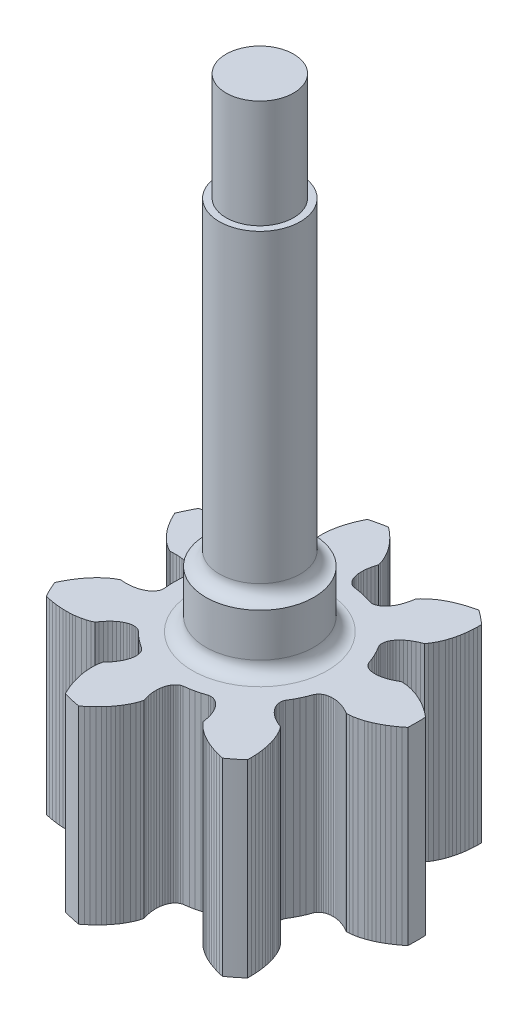
SolidWorks part; units mm, degrees
ref_plane "Front Plane" through (0, 0, 0) normal (0, 0, 1) x (1, 0, 0)
ref_plane "Top Plane" through (0, 0, 0) normal (0, 1, 0) x (1, 0, 0)
ref_plane "Right Plane" through (0, 0, 0) normal (1, 0, 0) x (0, 0, -1)
sketch "Sketch1" plane through (0, 0, 0) normal (0, 1, 0) x (1, 0, 0)
  circle A0 centre (0, 0) radius 2
  dimension "D1" = 4
extrude "Boss-Extrude1" add sketch "Sketch1" along normal blind 2.1
sketch "Sketch2" plane through (0, 2.1, 0) normal (0, 1, 0) x (1, 0, 0)
  circle A0 centre (0, 0) radius 1.5
  dimension "D1" = 3
extrude "Boss-Extrude3" add sketch "Sketch2" along normal blind 15.8
sketch "Sketch4" plane through (0, 0, 0) normal (0, -1, 0) x (1, 0, 0)
  line L420 (-1.6777, -5.4575) -> (-1.7402, -5.3144)
  line L421 (-1.7402, -5.3144) -> (-1.7939, -5.1757)
  line L422 (-1.7939, -5.1757) -> (-1.8392, -5.0423)
  line L423 (-1.8392, -5.0423) -> (-1.8764, -4.916)
  line L424 (-1.8764, -4.916) -> (-1.9071, -4.7932)
  line L425 (-1.9071, -4.7932) -> (-1.9311, -4.676)
  line L426 (-1.9311, -4.676) -> (-1.9488, -4.5668)
  line L427 (-1.9488, -4.5668) -> (-1.961, -4.464)
  line L428 (-1.961, -4.464) -> (-1.9715, -4.2798)
  line L429 (-1.9715, -4.2798) -> (-1.9674, -4.1246)
  line L430 (-1.9674, -4.1246) -> (-1.9537, -4.0009)
  line L431 (-1.9537, -4.0009) -> (-1.9303, -3.8867)
  line L432 (-1.9303, -3.8867) -> (-1.8594, -3.8097)
  line L433 (-1.8594, -3.8097) -> (-1.7784, -3.7125)
  line L434 (-1.7784, -3.7125) -> (-1.7087, -3.6155)
  line L435 (-1.7087, -3.6155) -> (-1.6501, -3.5195)
  line L436 (-1.6501, -3.5195) -> (-1.6023, -3.4251)
  line L437 (-1.6023, -3.4251) -> (-1.5652, -3.3333)
  line L438 (-1.5652, -3.3333) -> (-1.5384, -3.2446)
  line L439 (-1.5384, -3.2446) -> (-1.5215, -3.1597)
  line L440 (-1.5215, -3.1597) -> (-1.5143, -3.0795)
  line L441 (-1.5143, -3.0795) -> (-1.5162, -3.0043)
  line L442 (-1.5162, -3.0043) -> (-1.5269, -2.935)
  line L443 (-1.5269, -2.935) -> (-1.5457, -2.8721)
  line L444 (-1.5457, -2.8721) -> (-1.5723, -2.8162)
  line L445 (-1.5723, -2.8162) -> (-1.606, -2.7677)
  line L446 (-1.606, -2.7677) -> (-1.6572, -2.7183)
  line L447 (-1.6572, -2.7183) -> (-1.8447, -2.5928)
  line L448 (-1.8447, -2.5928) -> (-1.984, -2.4878)
  line L449 (-1.984, -2.4878) -> (-2.1173, -2.3754)
  line L450 (-2.1173, -2.3754) -> (-2.2814, -2.2205)
  line L451 (-2.2814, -2.2205) -> (-2.341, -2.1815)
  line L452 (-2.341, -2.1815) -> (-2.3957, -2.1595)
  line L453 (-2.3957, -2.1595) -> (-2.4562, -2.146)
  line L454 (-2.4562, -2.146) -> (-2.5217, -2.1417)
  line L455 (-2.5217, -2.1417) -> (-2.5917, -2.1467)
  line L456 (-2.5917, -2.1467) -> (-2.6653, -2.1615)
  line L457 (-2.6653, -2.1615) -> (-2.742, -2.1865)
  line L458 (-2.742, -2.1865) -> (-2.8209, -2.2218)
  line L459 (-2.8209, -2.2218) -> (-2.9014, -2.2676)
  line L460 (-2.9014, -2.2676) -> (-2.9827, -2.3243)
  line L461 (-2.9827, -2.3243) -> (-3.0641, -2.3918)
  line L462 (-3.0641, -2.3918) -> (-3.1447, -2.4703)
  line L463 (-3.1447, -2.4703) -> (-3.2237, -2.5599)
  line L464 (-3.2237, -2.5599) -> (-3.3005, -2.6605)
  line L465 (-3.3005, -2.6605) -> (-3.3598, -2.7467)
  line L466 (-3.3598, -2.7467) -> (-3.4659, -2.795)
  line L467 (-3.4659, -2.795) -> (-3.5835, -2.8358)
  line L468 (-3.5835, -2.8358) -> (-3.7338, -2.8744)
  line L469 (-3.7338, -2.8744) -> (-3.9158, -2.9052)
  line L470 (-3.9158, -2.9052) -> (-4.0187, -2.9161)
  line L471 (-4.0187, -2.9161) -> (-4.1291, -2.9232)
  line L472 (-4.1291, -2.9232) -> (-4.2487, -2.9258)
  line L473 (-4.2487, -2.9258) -> (-4.3752, -2.9233)
  line L474 (-4.3752, -2.9233) -> (-4.5067, -2.9151)
  line L475 (-4.5067, -2.9151) -> (-4.6468, -2.9006)
  line L476 (-4.6468, -2.9006) -> (-4.794, -2.8791)
  line L477 (-4.794, -2.8791) -> (-4.9474, -2.85)
  line L478 (-4.9474, -2.85) -> (-5.0902, -2.8167)
  line L479 (-5.3759, -2.2235) -> (-5.3129, -2.0911)
  line L480 (-5.3129, -2.0911) -> (-5.2399, -1.953)
  line L481 (-5.2399, -1.953) -> (-5.165, -1.8245)
  line L482 (-5.165, -1.8245) -> (-5.089, -1.7059)
  line L483 (-5.089, -1.7059) -> (-5.0134, -1.5981)
  line L484 (-5.0134, -1.5981) -> (-4.9365, -1.4976)
  line L485 (-4.9365, -1.4976) -> (-4.8599, -1.4057)
  line L486 (-4.8599, -1.4057) -> (-4.7855, -1.3238)
  line L487 (-4.7855, -1.3238) -> (-4.7128, -1.2502)
  line L488 (-4.7128, -1.2502) -> (-4.5753, -1.1271)
  line L489 (-4.5753, -1.1271) -> (-4.4514, -1.0336)
  line L490 (-4.4514, -1.0336) -> (-4.3462, -0.9671)
  line L491 (-4.3462, -0.9671) -> (-4.2422, -0.9142)
  line L492 (-4.2422, -0.9142) -> (-4.1379, -0.9217)
  line L493 (-4.1379, -0.9217) -> (-4.0114, -0.9244)
  line L494 (-4.0114, -0.9244) -> (-3.8921, -0.9184)
  line L495 (-3.8921, -0.9184) -> (-3.7804, -0.9043)
  line L496 (-3.7804, -0.9043) -> (-3.6769, -0.8828)
  line L497 (-3.6769, -0.8828) -> (-3.5819, -0.8546)
  line L498 (-3.5819, -0.8546) -> (-3.4959, -0.8203)
  line L499 (-3.4959, -0.8203) -> (-3.4191, -0.7805)
  line L500 (-3.4191, -0.7805) -> (-3.3518, -0.7361)
  line L501 (-3.3518, -0.7361) -> (-3.2942, -0.6878)
  line L502 (-3.2942, -0.6878) -> (-3.2467, -0.6363)
  line L503 (-3.2467, -0.6363) -> (-3.2093, -0.5823)
  line L504 (-3.2093, -0.5823) -> (-3.1821, -0.5267)
  line L505 (-3.1821, -0.5267) -> (-3.1652, -0.4701)
  line L506 (-3.1652, -0.4701) -> (-3.1585, -0.3992)
  line L507 (-3.1585, -0.3992) -> (-3.1773, -0.1744)
  line L508 (-3.1773, -0.1744) -> (-3.1821, 0)
  line L509 (-3.1821, 0) -> (-3.1773, 0.1743)
  line L510 (-3.1773, 0.1743) -> (-3.1585, 0.3991)
  line L511 (-3.1585, 0.3991) -> (-3.1652, 0.47)
  line L512 (-3.1652, 0.47) -> (-3.1821, 0.5266)
  line L513 (-3.1821, 0.5266) -> (-3.2093, 0.5822)
  line L514 (-3.2093, 0.5822) -> (-3.2467, 0.6362)
  line L515 (-3.2467, 0.6362) -> (-3.2942, 0.6877)
  line L516 (-3.2942, 0.6877) -> (-3.3518, 0.7361)
  line L517 (-3.3518, 0.7361) -> (-3.4191, 0.7805)
  line L518 (-3.4191, 0.7805) -> (-3.4959, 0.8202)
  line L519 (-3.4959, 0.8202) -> (-3.5819, 0.8545)
  line L520 (-3.5819, 0.8545) -> (-3.6769, 0.8828)
  line L521 (-3.6769, 0.8828) -> (-3.7804, 0.9043)
  line L522 (-3.7804, 0.9043) -> (-3.8921, 0.9183)
  line L523 (-3.8921, 0.9183) -> (-4.0114, 0.9243)
  line L524 (-4.0114, 0.9243) -> (-4.1379, 0.9216)
  line L525 (-4.1379, 0.9216) -> (-4.2422, 0.9142)
  line L526 (-4.2422, 0.9142) -> (-4.3462, 0.967)
  line L527 (-4.3462, 0.967) -> (-4.4514, 1.0335)
  line L528 (-4.4514, 1.0335) -> (-4.5753, 1.127)
  line L529 (-4.5753, 1.127) -> (-4.7128, 1.2501)
  line L530 (-4.7128, 1.2501) -> (-4.7855, 1.3238)
  line L531 (-4.7855, 1.3238) -> (-4.8599, 1.4056)
  line L532 (-4.8599, 1.4056) -> (-4.9365, 1.4975)
  line L533 (-4.9365, 1.4975) -> (-5.0134, 1.598)
  line L534 (-5.0134, 1.598) -> (-5.089, 1.7059)
  line L535 (-5.089, 1.7059) -> (-5.165, 1.8244)
  line L536 (-5.165, 1.8244) -> (-5.2399, 1.9529)
  line L537 (-5.2399, 1.9529) -> (-5.3129, 2.0911)
  line L538 (-5.3129, 2.0911) -> (-5.3759, 2.2234)
  line L539 (-5.0902, 2.8167) -> (-4.9474, 2.8499)
  line L540 (-4.9474, 2.8499) -> (-4.794, 2.879)
  line L541 (-4.794, 2.879) -> (-4.6468, 2.9005)
  line L542 (-4.6468, 2.9005) -> (-4.5067, 2.9151)
  line L543 (-4.5067, 2.9151) -> (-4.3752, 2.9232)
  line L544 (-4.3752, 2.9232) -> (-4.2487, 2.9257)
  line L545 (-4.2487, 2.9257) -> (-4.1291, 2.9231)
  line L546 (-4.1291, 2.9231) -> (-4.0187, 2.916)
  line L547 (-4.0187, 2.916) -> (-3.9158, 2.9051)
  line L548 (-3.9158, 2.9051) -> (-3.7338, 2.8743)
  line L549 (-3.7338, 2.8743) -> (-3.5835, 2.8358)
  line L550 (-3.5835, 2.8358) -> (-3.4659, 2.7949)
  line L551 (-3.4659, 2.7949) -> (-3.3598, 2.7466)
  line L552 (-3.3598, 2.7466) -> (-3.3005, 2.6604)
  line L553 (-3.3005, 2.6604) -> (-3.2237, 2.5598)
  line L554 (-3.2237, 2.5598) -> (-3.1447, 2.4703)
  line L555 (-3.1447, 2.4703) -> (-3.0641, 2.3918)
  line L556 (-3.0641, 2.3918) -> (-2.9827, 2.3242)
  line L557 (-2.9827, 2.3242) -> (-2.9014, 2.2676)
  line L558 (-2.9014, 2.2676) -> (-2.8209, 2.2217)
  line L559 (-2.8209, 2.2217) -> (-2.742, 2.1864)
  line L560 (-2.742, 2.1864) -> (-2.6653, 2.1615)
  line L561 (-2.6653, 2.1615) -> (-2.5917, 2.1466)
  line L562 (-2.5917, 2.1466) -> (-2.5217, 2.1416)
  line L563 (-2.5217, 2.1416) -> (-2.4562, 2.146)
  line L564 (-2.4562, 2.146) -> (-2.3957, 2.1594)
  line L565 (-2.3957, 2.1594) -> (-2.341, 2.1815)
  line L566 (-2.341, 2.1815) -> (-2.2814, 2.2205)
  line L567 (-2.2814, 2.2205) -> (-2.1173, 2.3753)
  line L568 (-2.1173, 2.3753) -> (-1.984, 2.4878)
  line L569 (-1.984, 2.4878) -> (-1.8447, 2.5927)
  line L570 (-1.8447, 2.5927) -> (-1.6572, 2.7182)
  line L571 (-1.6572, 2.7182) -> (-1.606, 2.7676)
  line L572 (-1.606, 2.7676) -> (-1.5723, 2.8161)
  line L573 (-1.5723, 2.8161) -> (-1.5457, 2.8721)
  line L574 (-1.5457, 2.8721) -> (-1.5269, 2.935)
  line L575 (-1.5269, 2.935) -> (-1.5162, 3.0043)
  line L576 (-1.5162, 3.0043) -> (-1.5143, 3.0794)
  line L577 (-1.5143, 3.0794) -> (-1.5215, 3.1597)
  line L578 (-1.5215, 3.1597) -> (-1.5384, 3.2445)
  line L579 (-1.5384, 3.2445) -> (-1.5652, 3.3332)
  line L580 (-1.5652, 3.3332) -> (-1.6023, 3.4251)
  line L581 (-1.6023, 3.4251) -> (-1.6501, 3.5194)
  line L582 (-1.6501, 3.5194) -> (-1.7087, 3.6154)
  line L583 (-1.7087, 3.6154) -> (-1.7784, 3.7125)
  line L584 (-1.7784, 3.7125) -> (-1.8594, 3.8097)
  line L585 (-1.8594, 3.8097) -> (-1.9303, 3.8866)
  line L586 (-1.9303, 3.8866) -> (-1.9537, 4.0009)
  line L587 (-1.9537, 4.0009) -> (-1.9674, 4.1246)
  line L588 (-1.9674, 4.1246) -> (-1.9715, 4.2797)
  line L589 (-1.9715, 4.2797) -> (-1.961, 4.464)
  line L590 (-1.961, 4.464) -> (-1.9488, 4.5668)
  line L591 (-1.9488, 4.5668) -> (-1.9311, 4.6759)
  line L592 (-1.9311, 4.6759) -> (-1.9071, 4.7932)
  line L593 (-1.9071, 4.7932) -> (-1.8764, 4.9159)
  line L594 (-1.8764, 4.9159) -> (-1.8392, 5.0423)
  line L595 (-1.8392, 5.0423) -> (-1.7939, 5.1756)
  line L596 (-1.7939, 5.1756) -> (-1.7402, 5.3143)
  line L597 (-1.7402, 5.3143) -> (-1.6777, 5.4575)
  line L598 (-1.6777, 5.4575) -> (-1.6135, 5.5893)
  line L599 (-0.9715, 5.7358) -> (-0.8565, 5.6449)
  line L600 (-0.8565, 5.6449) -> (-0.7381, 5.543)
  line L601 (-0.7381, 5.543) -> (-0.6295, 5.4414)
  line L602 (-0.6295, 5.4414) -> (-0.5308, 5.3409)
  line L603 (-0.5308, 5.3409) -> (-0.4425, 5.2432)
  line L604 (-0.4425, 5.2432) -> (-0.3616, 5.1459)
  line L605 (-0.3616, 5.1459) -> (-0.2891, 5.0507)
  line L606 (-0.2891, 5.0507) -> (-0.2258, 4.96)
  line L607 (-0.2258, 4.96) -> (-0.1702, 4.8727)
  line L608 (-0.1702, 4.8727) -> (-0.0808, 4.7113)
  line L609 (-0.0808, 4.7113) -> (-0.0172, 4.5697)
  line L610 (-0.0172, 4.5697) -> (0.0242, 4.4523)
  line L611 (0.0242, 4.4523) -> (0.0526, 4.3392)
  line L612 (0.0526, 4.3392) -> (0.0222, 4.2391)
  line L613 (0.0222, 4.2391) -> (-0.0086, 4.1164)
  line L614 (-0.0086, 4.1164) -> (-0.0293, 3.9987)
  line L615 (-0.0293, 3.9987) -> (-0.0405, 3.8868)
  line L616 (-0.0405, 3.8868) -> (-0.0426, 3.7811)
  line L617 (-0.0426, 3.7811) -> (-0.0362, 3.6822)
  line L618 (-0.0362, 3.6822) -> (-0.0218, 3.5907)
  line L619 (-0.0218, 3.5907) -> (-0.0002, 3.5069)
  line L620 (-0.0002, 3.5069) -> (0.0281, 3.4314)
  line L621 (0.0281, 3.4314) -> (0.0624, 3.3646)
  line L622 (0.0624, 3.3646) -> (0.1021, 3.3068)
  line L623 (0.1021, 3.3068) -> (0.1464, 3.2583)
  line L624 (0.1464, 3.2583) -> (0.1946, 3.2194)
  line L625 (0.1946, 3.2194) -> (0.246, 3.1903)
  line L626 (0.246, 3.1903) -> (0.3136, 3.1681)
  line L627 (0.3136, 3.1681) -> (0.537, 3.1363)
  line L628 (0.537, 3.1363) -> (0.708, 3.1022)
  line L629 (0.708, 3.1022) -> (0.8769, 3.0588)
  line L630 (0.8769, 3.0588) -> (1.0919, 2.9904)
  line L631 (1.0919, 2.9904) -> (1.1625, 2.9811)
  line L632 (1.1625, 2.9811) -> (1.2214, 2.985)
  line L633 (1.2214, 2.985) -> (1.2817, 2.9991)
  line L634 (1.2817, 2.9991) -> (1.3427, 3.0236)
  line L635 (1.3427, 3.0236) -> (1.4035, 3.0585)
  line L636 (1.4035, 3.0585) -> (1.4634, 3.1038)
  line L637 (1.4634, 3.1038) -> (1.5217, 3.1596)
  line L638 (1.5217, 3.1596) -> (1.5775, 3.2256)
  line L639 (1.5775, 3.2256) -> (1.6301, 3.3019)
  line L640 (1.6301, 3.3019) -> (1.6788, 3.3882)
  line L641 (1.6788, 3.3882) -> (1.7228, 3.4843)
  line L642 (1.7228, 3.4843) -> (1.7613, 3.59)
  line L643 (1.7613, 3.59) -> (1.7937, 3.705)
  line L644 (1.7937, 3.705) -> (1.8192, 3.829)
  line L645 (1.8192, 3.829) -> (1.8352, 3.9324)
  line L646 (1.8352, 3.9324) -> (1.9099, 4.0219)
  line L647 (1.9099, 4.0219) -> (1.9981, 4.1097)
  line L648 (1.9981, 4.1097) -> (2.1168, 4.2097)
  line L649 (2.1168, 4.2097) -> (2.2674, 4.3164)
  line L650 (2.2674, 4.3164) -> (2.3554, 4.3709)
  line L651 (2.3554, 4.3709) -> (2.4518, 4.4251)
  line L652 (2.4518, 4.4251) -> (2.5584, 4.4794)
  line L653 (2.5584, 4.4794) -> (2.6735, 4.532)
  line L654 (2.6735, 4.532) -> (2.7955, 4.5817)
  line L655 (2.7955, 4.5817) -> (2.928, 4.6294)
  line L656 (2.928, 4.6294) -> (3.0699, 4.6739)
  line L657 (3.0699, 4.6739) -> (3.2208, 4.7143)
  line L658 (3.2208, 4.7143) -> (3.3639, 4.7463)
  line L659 (3.8787, 4.3357) -> (3.8793, 4.1891)
  line L660 (3.8793, 4.1891) -> (3.8735, 4.033)
  line L661 (3.8735, 4.033) -> (3.8618, 3.8847)
  line L662 (3.8618, 3.8847) -> (3.8448, 3.7449)
  line L663 (3.8448, 3.7449) -> (3.8234, 3.615)
  line L664 (3.8234, 3.615) -> (3.7978, 3.4911)
  line L665 (3.7978, 3.4911) -> (3.7686, 3.375)
  line L666 (3.7686, 3.375) -> (3.7371, 3.269)
  line L667 (3.7371, 3.269) -> (3.7036, 3.1711)
  line L668 (3.7036, 3.1711) -> (3.6331, 3.0005)
  line L669 (3.6331, 3.0005) -> (3.562, 2.8625)
  line L670 (3.562, 2.8625) -> (3.4961, 2.757)
  line L671 (3.4961, 2.757) -> (3.4253, 2.6643)
  line L672 (3.4253, 2.6643) -> (3.3281, 2.6257)
  line L673 (3.3281, 2.6257) -> (3.213, 2.5732)
  line L674 (3.213, 2.5732) -> (3.1081, 2.516)
  line L675 (3.1081, 2.516) -> (3.0136, 2.4549)
  line L676 (3.0136, 2.4549) -> (2.9296, 2.3907)
  line L677 (2.9296, 2.3907) -> (2.8563, 2.324)
  line L678 (2.8563, 2.324) -> (2.7937, 2.2557)
  line L679 (2.7937, 2.2557) -> (2.7417, 2.1866)
  line L680 (2.7417, 2.1866) -> (2.7003, 2.1174)
  line L681 (2.7003, 2.1174) -> (2.6695, 2.0489)
  line L682 (2.6695, 2.0489) -> (2.649, 1.9819)
  line L683 (2.649, 1.9819) -> (2.6387, 1.917)
  line L684 (2.6387, 1.917) -> (2.6383, 1.8551)
  line L685 (2.6383, 1.8551) -> (2.6476, 1.7967)
  line L686 (2.6476, 1.7967) -> (2.6724, 1.73)
  line L687 (2.6724, 1.73) -> (2.7869, 1.5356)
  line L688 (2.7869, 1.5356) -> (2.8668, 1.3806)
  line L689 (2.8668, 1.3806) -> (2.9382, 1.2215)
  line L690 (2.9382, 1.2215) -> (3.0188, 1.0107)
  line L691 (3.0188, 1.0107) -> (3.0555, 0.9498)
  line L692 (3.0555, 0.9498) -> (3.0953, 0.9061)
  line L693 (3.0953, 0.9061) -> (3.144, 0.8678)
  line L694 (3.144, 0.8678) -> (3.2011, 0.8354)
  line L695 (3.2011, 0.8354) -> (3.2663, 0.8096)
  line L696 (3.2663, 0.8096) -> (3.3391, 0.791)
  line L697 (3.3391, 0.791) -> (3.419, 0.7802)
  line L698 (3.419, 0.7802) -> (3.5054, 0.7777)
  line L699 (3.5054, 0.7777) -> (3.5979, 0.7842)
  line L700 (3.5979, 0.7842) -> (3.6957, 0.7999)
  line L701 (3.6957, 0.7999) -> (3.7983, 0.8255)
  line L702 (3.7983, 0.8255) -> (3.905, 0.8612)
  line L703 (3.905, 0.8612) -> (4.0151, 0.9076)
  line L704 (4.0151, 0.9076) -> (4.1279, 0.9649)
  line L705 (4.1279, 0.9649) -> (4.2187, 1.0169)
  line L706 (4.2187, 1.0169) -> (4.3353, 1.0144)
  line L707 (4.3353, 1.0144) -> (4.4589, 1.0001)
  line L708 (4.4589, 1.0001) -> (4.6111, 0.9696)
  line L709 (4.6111, 0.9696) -> (4.7884, 0.9184)
  line L710 (4.7884, 0.9184) -> (4.8859, 0.8836)
  line L711 (4.8859, 0.8836) -> (4.9884, 0.8421)
  line L712 (4.9884, 0.8421) -> (5.0973, 0.7926)
  line L713 (5.0973, 0.7926) -> (5.2102, 0.7354)
  line L714 (5.2102, 0.7354) -> (5.3251, 0.671)
  line L715 (5.3251, 0.671) -> (5.445, 0.5972)
  line L716 (5.445, 0.5972) -> (5.5683, 0.5139)
  line L717 (5.5683, 0.5139) -> (5.6939, 0.4211)
  line L718 (5.6939, 0.4211) -> (5.8081, 0.3292)
  line L719 (5.8081, -0.3293) -> (5.6939, -0.4212)
  line L720 (5.6939, -0.4212) -> (5.5683, -0.514)
  line L721 (5.5683, -0.514) -> (5.445, -0.5972)
  line L722 (5.445, -0.5972) -> (5.3251, -0.6711)
  line L723 (5.3251, -0.6711) -> (5.2102, -0.7354)
  line L724 (5.2102, -0.7354) -> (5.0973, -0.7926)
  line L725 (5.0973, -0.7926) -> (4.9884, -0.8421)
  line L726 (4.9884, -0.8421) -> (4.8859, -0.8837)
  line L727 (4.8859, -0.8837) -> (4.7884, -0.9185)
  line L728 (4.7884, -0.9185) -> (4.6111, -0.9697)
  line L729 (4.6111, -0.9697) -> (4.4589, -1.0002)
  line L730 (4.4589, -1.0002) -> (4.3353, -1.0144)
  line L731 (4.3353, -1.0144) -> (4.2187, -1.017)
  line L732 (4.2187, -1.017) -> (4.1279, -0.965)
  line L733 (4.1279, -0.965) -> (4.0151, -0.9077)
  line L734 (4.0151, -0.9077) -> (3.905, -0.8613)
  line L735 (3.905, -0.8613) -> (3.7983, -0.8255)
  line L736 (3.7983, -0.8255) -> (3.6957, -0.8)
  line L737 (3.6957, -0.8) -> (3.5979, -0.7842)
  line L738 (3.5979, -0.7842) -> (3.5054, -0.7778)
  line L739 (3.5054, -0.7778) -> (3.419, -0.7803)
  line L740 (3.419, -0.7803) -> (3.3391, -0.7911)
  line L741 (3.3391, -0.7911) -> (3.2663, -0.8097)
  line L742 (3.2663, -0.8097) -> (3.2011, -0.8354)
  line L743 (3.2011, -0.8354) -> (3.144, -0.8678)
  line L744 (3.144, -0.8678) -> (3.0953, -0.9062)
  line L745 (3.0953, -0.9062) -> (3.0555, -0.9498)
  line L746 (3.0555, -0.9498) -> (3.0188, -1.0108)
  line L747 (3.0188, -1.0108) -> (2.9382, -1.2215)
  line L748 (2.9382, -1.2215) -> (2.8668, -1.3806)
  line L749 (2.8668, -1.3806) -> (2.7869, -1.5356)
  line L750 (2.7869, -1.5356) -> (2.6724, -1.7301)
  line L751 (2.6724, -1.7301) -> (2.6476, -1.7968)
  line L752 (2.6476, -1.7968) -> (2.6383, -1.8551)
  line L753 (2.6383, -1.8551) -> (2.6387, -1.9171)
  line L754 (2.6387, -1.9171) -> (2.649, -1.9819)
  line L755 (2.649, -1.9819) -> (2.6695, -2.049)
  line L756 (2.6695, -2.049) -> (2.7003, -2.1175)
  line L757 (2.7003, -2.1175) -> (2.7417, -2.1867)
  line L758 (2.7417, -2.1867) -> (2.7937, -2.2558)
  line L759 (2.7937, -2.2558) -> (2.8563, -2.3241)
  line L760 (2.8563, -2.3241) -> (2.9296, -2.3907)
  line L761 (2.9296, -2.3907) -> (3.0136, -2.455)
  line L762 (3.0136, -2.455) -> (3.1081, -2.5161)
  line L763 (3.1081, -2.5161) -> (3.213, -2.5733)
  line L764 (3.213, -2.5733) -> (3.3281, -2.6257)
  line L765 (3.3281, -2.6257) -> (3.4253, -2.6643)
  line L766 (3.4253, -2.6643) -> (3.4961, -2.757)
  line L767 (3.4961, -2.757) -> (3.562, -2.8626)
  line L768 (3.562, -2.8626) -> (3.6331, -3.0006)
  line L769 (3.6331, -3.0006) -> (3.7036, -3.1711)
  line L770 (3.7036, -3.1711) -> (3.7371, -3.2691)
  line L771 (3.7371, -3.2691) -> (3.7686, -3.3751)
  line L772 (3.7686, -3.3751) -> (3.7978, -3.4911)
  line L773 (3.7978, -3.4911) -> (3.8234, -3.615)
  line L774 (3.8234, -3.615) -> (3.8448, -3.745)
  line L775 (3.8448, -3.745) -> (3.8618, -3.8848)
  line L776 (3.8618, -3.8848) -> (3.8735, -4.0331)
  line L777 (3.8735, -4.0331) -> (3.8793, -4.1892)
  line L778 (3.8793, -4.1892) -> (3.8787, -4.3358)
  line L779 (3.3639, -4.7463) -> (3.2208, -4.7143)
  line L780 (3.2208, -4.7143) -> (3.0699, -4.6739)
  line L781 (3.0699, -4.6739) -> (2.928, -4.6295)
  line L782 (2.928, -4.6295) -> (2.7955, -4.5818)
  line L783 (2.7955, -4.5818) -> (2.6735, -4.5321)
  line L784 (2.6735, -4.5321) -> (2.5584, -4.4795)
  line L785 (2.5584, -4.4795) -> (2.4518, -4.4252)
  line L786 (2.4518, -4.4252) -> (2.3554, -4.3709)
  line L787 (2.3554, -4.3709) -> (2.2674, -4.3164)
  line L788 (2.2674, -4.3164) -> (2.1168, -4.2097)
  line L789 (2.1168, -4.2097) -> (1.9981, -4.1098)
  line L790 (1.9981, -4.1098) -> (1.9099, -4.022)
  line L791 (1.9099, -4.022) -> (1.8352, -3.9324)
  line L792 (1.8352, -3.9324) -> (1.8192, -3.829)
  line L793 (1.8192, -3.829) -> (1.7937, -3.7051)
  line L794 (1.7937, -3.7051) -> (1.7613, -3.5901)
  line L795 (1.7613, -3.5901) -> (1.7228, -3.4844)
  line L796 (1.7228, -3.4844) -> (1.6788, -3.3883)
  line L797 (1.6788, -3.3883) -> (1.6301, -3.3019)
  line L798 (1.6301, -3.3019) -> (1.5775, -3.2257)
  line L799 (1.5775, -3.2257) -> (1.5217, -3.1596)
  line L800 (1.5217, -3.1596) -> (1.4634, -3.1039)
  line L801 (1.4634, -3.1039) -> (1.4035, -3.0586)
  line L802 (1.4035, -3.0586) -> (1.3427, -3.0237)
  line L803 (1.3427, -3.0237) -> (1.2817, -2.9992)
  line L804 (1.2817, -2.9992) -> (1.2214, -2.9851)
  line L805 (1.2214, -2.9851) -> (1.1625, -2.9812)
  line L806 (1.1625, -2.9812) -> (1.0919, -2.9905)
  line L807 (1.0919, -2.9905) -> (0.8769, -3.0588)
  line L808 (0.8769, -3.0588) -> (0.708, -3.1023)
  line L809 (0.708, -3.1023) -> (0.537, -3.1364)
  line L810 (0.537, -3.1364) -> (0.3136, -3.1681)
  line L811 (0.3136, -3.1681) -> (0.246, -3.1904)
  line L812 (0.246, -3.1904) -> (0.1946, -3.2194)
  line L813 (0.1946, -3.2194) -> (0.1464, -3.2583)
  line L814 (0.1464, -3.2583) -> (0.1021, -3.3068)
  line L815 (0.1021, -3.3068) -> (0.0624, -3.3647)
  line L816 (0.0624, -3.3647) -> (0.0281, -3.4315)
  line L817 (0.0281, -3.4315) -> (-0.0002, -3.507)
  line L818 (-0.0002, -3.507) -> (-0.0218, -3.5907)
  line L819 (-0.0218, -3.5907) -> (-0.0362, -3.6823)
  line L820 (-0.0362, -3.6823) -> (-0.0426, -3.7811)
  line L821 (-0.0426, -3.7811) -> (-0.0405, -3.8868)
  line L822 (-0.0405, -3.8868) -> (-0.0293, -3.9988)
  line L823 (-0.0293, -3.9988) -> (-0.0086, -4.1165)
  line L824 (-0.0086, -4.1165) -> (0.0222, -4.2392)
  line L825 (0.0222, -4.2392) -> (0.0526, -4.3393)
  line L826 (0.0526, -4.3393) -> (0.0242, -4.4524)
  line L827 (0.0242, -4.4524) -> (-0.0172, -4.5698)
  line L828 (-0.0172, -4.5698) -> (-0.0808, -4.7113)
  line L829 (-0.0808, -4.7113) -> (-0.1702, -4.8728)
  line L830 (-0.1702, -4.8728) -> (-0.2258, -4.9601)
  line L831 (-0.2258, -4.9601) -> (-0.2891, -5.0508)
  line L832 (-0.2891, -5.0508) -> (-0.3616, -5.146)
  line L833 (-0.3616, -5.146) -> (-0.4425, -5.2433)
  line L834 (-0.4425, -5.2433) -> (-0.5308, -5.341)
  line L835 (-0.5308, -5.341) -> (-0.6295, -5.4414)
  line L836 (-0.6295, -5.4414) -> (-0.7381, -5.5431)
  line L837 (-0.7381, -5.5431) -> (-0.8565, -5.645)
  line L838 (-0.8565, -5.645) -> (-0.9715, -5.7359)
  line L839 (-1.6135, -5.5894) -> (-1.6777, -5.4575)
  arc A7 (-5.3759, -2.2235) -> (-5.0902, -2.8167) centre (0, 0) ccw
  arc A8 (-5.0902, 2.8167) -> (-5.3759, 2.2234) centre (0, -0.0001) ccw
  arc A9 (-0.9715, 5.7358) -> (-1.6135, 5.5893) centre (0, -0.0001) ccw
  arc A10 (3.8787, 4.3357) -> (3.3639, 4.7463) centre (-0.0001, -0.0001) ccw
  arc A11 (5.8081, -0.3293) -> (5.8081, 0.3292) centre (-0.0001, 0) ccw
  arc A12 (3.3639, -4.7463) -> (3.8787, -4.3358) centre (-0.0001, 0) ccw
  arc A13 (-1.6135, -5.5894) -> (-0.9715, -5.7359) centre (0, 0) ccw
extrude "Boss-Extrude4" add sketch "Sketch4" along normal blind 7
sketch "Sketch3" plane through (0, 0, 0) normal (0, -1, 0) x (1, 0, 0)
  circle A0 centre (0, 0) radius 1.1
  circle A1 centre (0, 0) radius 0.75
  dimension "D1" = 2.2
  dimension "D2" = 1.5
extrude "Cut-Extrude2" cut sketch "Sketch3" along normal through all contours A0 A1 | A1 region at (-1.0689, 0, 0) region at (0, 0, 0)
fillet "Fillet1" radius 0.5 2 edges at (0, 2.1, 1.5) (0, 0, -2)
chamfer "Chamfer1" distance 0.4 angle 45 2 edges at (0, 0, 1.1) (0, -7, 1.1)
ref_plane "Plane1" through (0, 2.1, 0) normal (0, -1, 0) x (-1, 0, 0)
ref_plane "Plane for bottom of support plate" through (0, 8.1, 0) normal (0, -1, 0) x (-1, 0, 0)
sketch "Sketch5" plane through (0, 17.9, 0) normal (0, 1, 0) x (1, 0, 0)
  circle A0 centre (0, 0) radius 1.5
  circle A1 centre (0, 0) radius 1.5 construction
  circle A2 centre (0, 0) radius 1.25
  dimension "D1" = 0.25
extrude "Cut-Extrude3" cut sketch "Sketch5" against normal blind 4
ref_plane "Plane for end of coupler" through (0, 12.1, 0) normal (0, -1, 0) x (-1, 0, 0)
ref_plane "Plane for end of torque spline sleeve" through (0, 13.1, 0) normal (0, -1, 0) x (-1, 0, 0)
